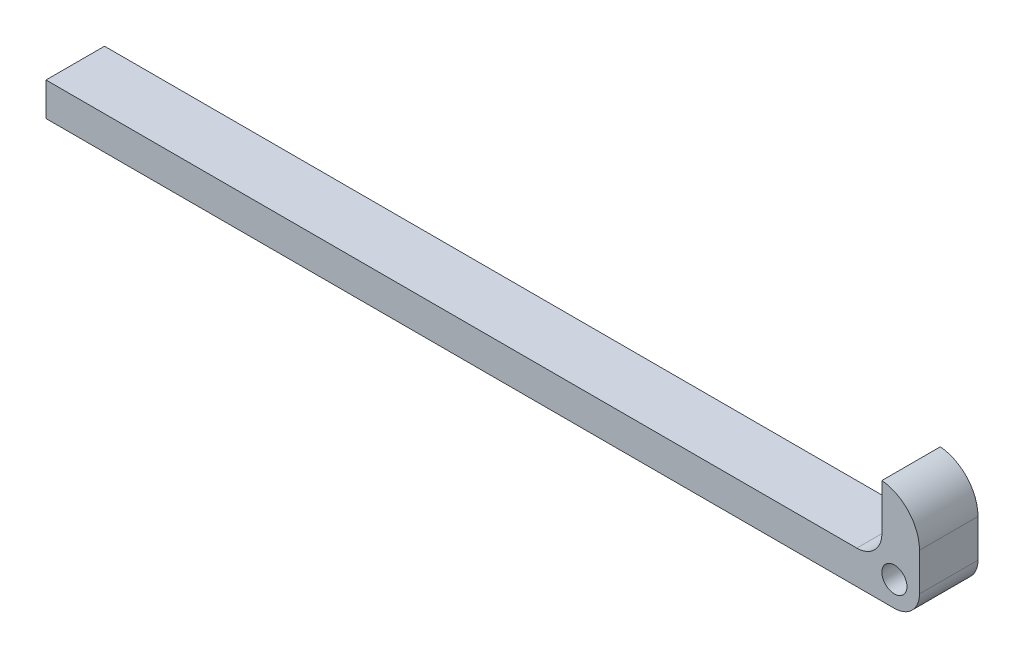
SolidWorks part; units mm, degrees
ref_plane "Спереди" through (0, 0, 0) normal (0, 0, 1) x (1, 0, 0)
ref_plane "Сверху" through (0, 0, 0) normal (0, 1, 0) x (1, 0, 0)
ref_plane "Справа" through (0, 0, 0) normal (1, 0, 0) x (0, 0, -1)
sketch "Эскиз1" plane through (0, 36.6972, 0) normal (0, 1, 0) x (1, 0, 0)
  line L5 (-14, -4) -> (-9, -4)
  line L6 (-14, 4) -> (-14, -4)
  line L7 (-9, 4) -> (-14, 4)
  line L8 (-9, -4) -> (-9, 4)
  line L17 (-14, -3.5) -> (-9.5, -3.5)
  line L18 (-9.5, -3.5) -> (-9.5, 3.5)
  line L19 (-9.5, 3.5) -> (-14, 3.5)
  line L68 (-14, 3.5) -> (-14, -3.5)
  dimension "D1" = 0
extrude "Бобышка-Вытянуть1" add sketch "Эскиз1" along normal blind 5 and the other way blind 7.5
sketch "Эскиз2" plane through (0, 29.1972, 0) normal (0, -1, 0) x (1, 0, 0)
  line L19 (-14, -3.5) -> (-14, 3.5)
  line L22 (-14, 3.5) -> (-9.5, 3.5)
  line L23 (-9.5, -3.5) -> (-14, -3.5)
  line L24 (-9.5, 3.5) -> (-9.5, -3.5)
  line L25 (-14, 3.5) -> (-9.5, 3.5)
  line L26 (-9.5, -3.5) -> (-14, -3.5)
  line L27 (-9.5, 3.5) -> (-9.5, -3.5)
  dimension "D1" = 0.5
extrude "Бобышка-Вытянуть2" add sketch "Эскиз2" against normal blind 4
fillet "Скругление1" radius 3 1 edges at (-9.5, 29.1972, 0)
ref_axis "Ось1" through (-12.5, 32.1972, -3.5) along (0, 0, 1)
sketch "Эскиз3" plane through (-14, 0, 0) normal (-1, 0, 0) x (0, 0, 1)
  line L1 (-3.5, 29.1972) -> (-3.5, 33.1972)
  line L3 (-3.5, 29.1972) -> (3.5, 29.1972)
  line L5 (3.5, 29.1972) -> (3.5, 33.1972)
  line L6 (-3.5, 33.1972) -> (3.5, 33.1972)
  dimension "D1" = 4
extrude "Бобышка-Вытянуть3" add sketch "Эскиз3" along normal blind 100
ref_plane "Плоскость1" through (-9.5, 41.6972, -3.5) normal (0, 0, -1) x (-1, 0, 0)
ref_plane "Плоскость2" through (-9.5, 41.6972, -3.5) normal (0, 0, -1) x (-1, 0, 0)
fillet "Скругление2" radius 5 1 edges at (-9.5, 41.6972, 0)
fillet "Скругление3" radius 3 1 edges at (-14, 33.1972, 0)
sketch "Эскиз6" plane through (0, 0, 0) normal (0, 0, 1) x (1, 0, 0)
  circle A0 centre (-12.5, 32.1972) radius 1.5
  dimension "D1" = 3
extrude "Вырез-Вытянуть1" cut sketch "Эскиз6" against normal through all and the other way through all
